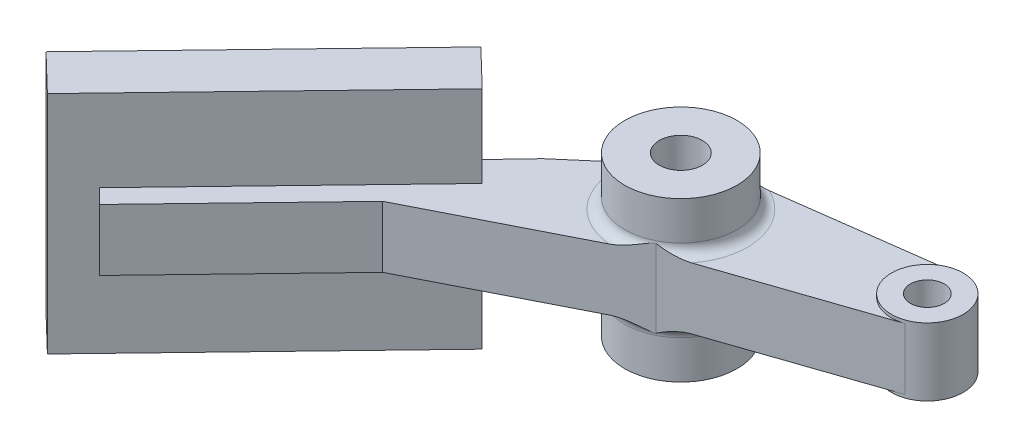
SolidWorks part; units mm, degrees
ref_plane "前视基准面" through (0, 0, 0) normal (0, 0, 1) x (1, 0, 0)
ref_plane "上视基准面" through (0, 0, 0) normal (0, 1, 0) x (1, 0, 0)
ref_plane "右视基准面" through (0, 0, 0) normal (1, 0, 0) x (0, 0, -1)
sketch "草图1" plane through (0, 0, 0) normal (0, 1, 0) x (1, 0, 0)
  line L0 (-11.0036, -2.4912) -> (-19.5145, -11.4449)
  line L1 (-28.7504, -27.9753) -> (-32.0487, -24.6312)
  line L2 (-11.0036, -2.4912) -> (-4.5897, 3.0306)
  line L4 (-15.1995, -13.8916) -> (2.4913, -4.9034)
  line L5 (0, 5.5) -> (19.0062, 8.042)
  line L6 (2.4913, -4.9034) -> (20.598, 1.2596)
  line L7 (-19.5145, -11.4449) -> (-32.0487, -24.6312)
  line L12 (-15.1995, -13.8916) -> (-28.7504, -27.9753)
  arc A0 (0, 5.5) -> (-4.5897, 3.0306) centre (0, 0) ccw
  arc A2 (20.598, 1.2596) -> (19.0062, 8.042) centre (19.4702, 4.5729) ccw
  dimension "D1" = 11
  dimension "D6" = 7
  dimension "D2" = 20
extrude "拉伸1" add sketch "草图1" along normal blind 6
ref_plane "基准面1" through (0, 3, 0) normal (0, -1, 0) x (1, 0, 0)
sketch "草图4" plane through (0, 3, 0) normal (0, -1, 0) x (1, 0, 0)
  circle A0 centre (19.4702, -4.5729) radius 3.5
extrude "拉伸2" add sketch "草图4" along normal mid plane 6.6
sketch "草图5" plane through (0, 3, 0) normal (0, -1, 0) x (1, 0, 0)
  circle A0 centre (19.4702, -4.5729) radius 1.65
  dimension "D1" = 3.3
extrude "拉伸5" cut sketch "草图5" against normal mid plane 6.6
sketch "草图7" plane through (0, 3, 0) normal (0, -1, 0) x (1, 0, 0)
  circle A0 centre (0, 0) radius 5.4793
extrude "拉伸6" add sketch "草图7" along normal mid plane 15.5
sketch "草图8" plane through (0, 3, 0) normal (0, -1, 0) x (1, 0, 0)
  circle A0 centre (0, 0) radius 2.1
  dimension "D1" = 4.2
extrude "拉伸7" cut sketch "草图8" against normal mid plane 15.5
fillet "圆角1" radius 1 1 edges at (0, 0, 5.4793)
fillet "圆角2" radius 1 1 edges at (0, 6, 5.4793)
sketch "草图9" plane through (0, 3, 0) normal (0, -1, 0) x (1, 0, 0)
  line L0 (-32.6504, 29.1441) -> (-11.8501, 7.5259)
  line L2 (-11.8501, 7.5259) -> (-15.4532, 4.0592)
  line L3 (-15.4532, 4.0592) -> (-36.2535, 25.6774)
  line L4 (-36.2535, 25.6774) -> (-32.6504, 29.1441)
  line L5 (-28.7504, 27.9753) -> (-15.1995, 13.8916) construction
  dimension "D1" = 5
  dimension "D2" = 30
  dimension "D3" = 7
extrude "拉伸8" add sketch "草图9" along normal mid plane 22
